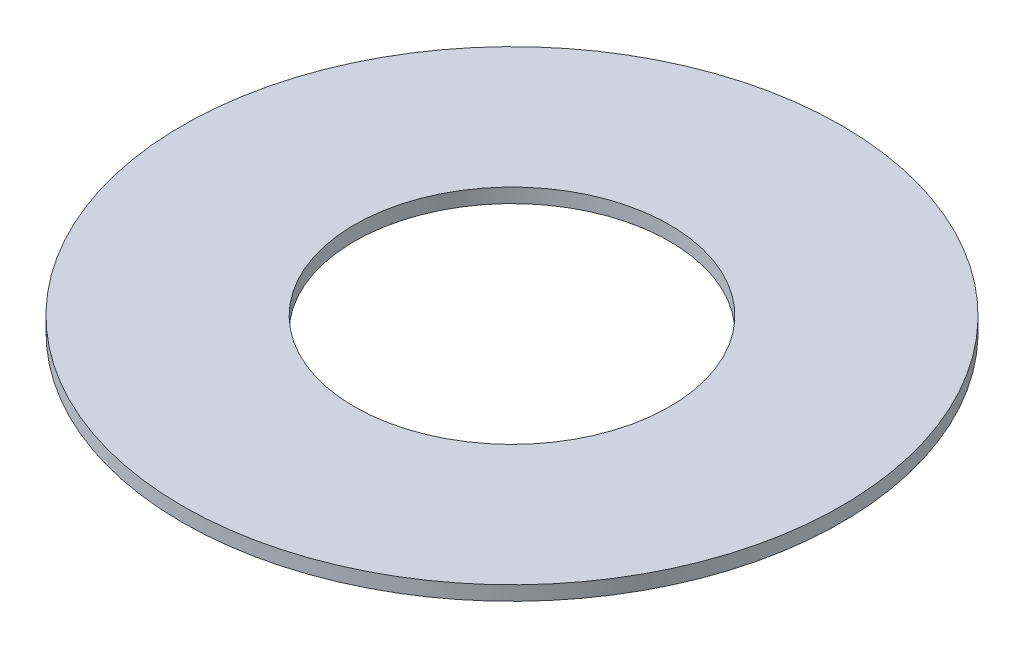
SolidWorks part; units mm, degrees
material "PTFE (general)"
ref_plane "Front Plane" through (0, 0, 0) normal (0, 0, 1) x (1, 0, 0)
ref_plane "Top Plane" through (0, 0, 0) normal (0, 1, 0) x (1, 0, 0)
ref_plane "Right Plane" through (0, 0, 0) normal (1, 0, 0) x (0, 0, -1)
sketch "Sketch1" plane through (0, 0, 0) normal (0, 1, 0) x (1, 0, 0)
  circle A0 centre (0, 0) radius 46
  dimension "D2" = 92
extrude "Boss-Extrude1" add sketch "Sketch1" along normal blind 2
sketch "Sketch2" plane through (0, 2, 0) normal (0, 1, 0) x (1, 0, 0)
  line L0 (8.6667, 0) -> (-17.7957, 0) construction
  line L1 (-17.7957, 0) -> (0, 0) construction
  line L2 (-12.5, 0) -> (0, 0) construction
  circle A2 centre (-12.5, 0) radius 0.25
  dimension "D1" = 0.5
  dimension "D2" = 12.5
  dimension "D5" = 0
extrude "Cut-Extrude1" cut sketch "Sketch2" against normal through all both and the other way through all
sketch "Sketch3" plane through (0, 2, 0) normal (0, 1, 0) x (1, 0, 0)
  line L1 (0, 0) -> (0, 12.5) construction
  line L2 (0, 12.5) -> (0, 0) construction
  line L3 (0, 0) -> (7.8426, -29.2691) construction
  circle A1 centre (3.1058, -11.5911) radius 1
  dimension "D3" = 2
  dimension "D4" = 12
  dimension "D5" = 15
extrude "Cut-Extrude2" cut sketch "Sketch3" against normal through all both and the other way through all
sketch "Sketch4" plane through (0, 2, 0) normal (0, 1, 0) x (1, 0, 0)
  line L0 (-16.9145, 6.1564) -> (0, 0) construction
  line L1 (0, 0) -> (0, -18) construction
  line L2 (0, -18) -> (0, 0) construction
  line L3 (0, 0) -> (16.9145, 6.1564) construction
  circle A0 centre (0, 0) radius 18
  circle A1 centre (0, -18) radius 1
  circle A2 centre (-16.9145, 6.1564) radius 1
  circle A3 centre (16.9145, 6.1564) radius 1
  dimension "D1" = 2
  dimension "D2" = 2
  dimension "D3" = 2
  dimension "D4" = 36
  dimension "D5" = 110
  dimension "D6" = 140
extrude "Cut-Extrude3" cut sketch "Sketch4" against normal blind 1 contours A1 | A2 | A3
sketch "Sketch5" plane through (0, 2, 0) normal (0, 1, 0) x (1, 0, 0)
  circle A0 centre (0, 0) radius 22
  dimension "D1" = 44
extrude "Cut-Extrude4" cut sketch "Sketch5" against normal blind 10
